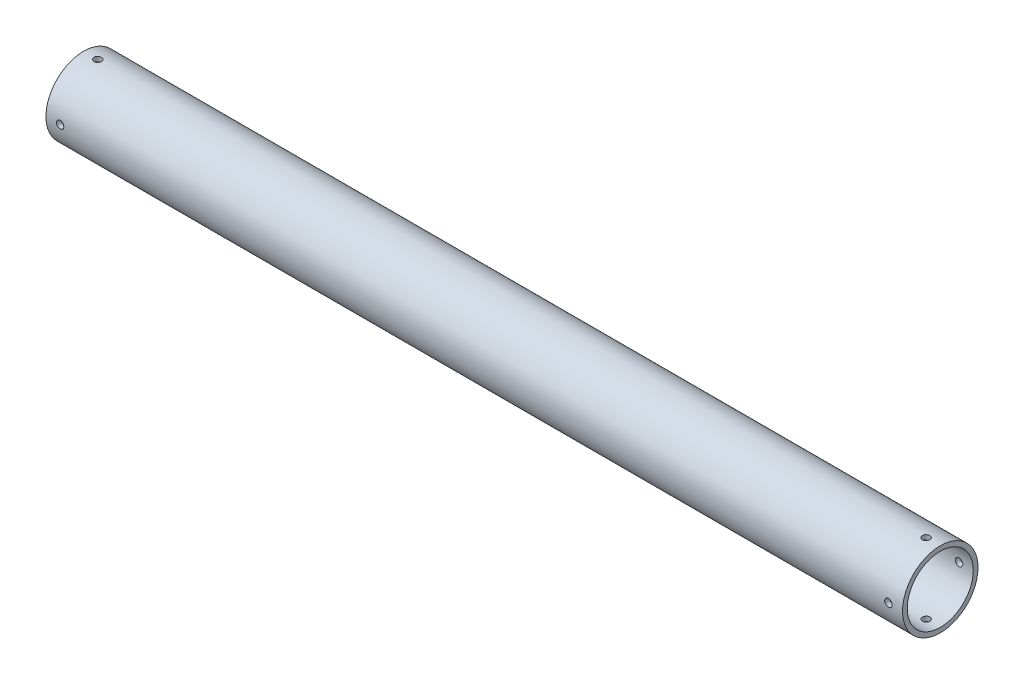
SolidWorks part; units mm, degrees
material "PC High Viscosity"
ref_plane "Front Plane" through (0, 0, 0) normal (0, 0, 1) x (1, 0, 0)
ref_plane "Top Plane" through (0, 0, 0) normal (0, 1, 0) x (1, 0, 0)
ref_plane "Right Plane" through (0, 0, 0) normal (1, 0, 0) x (0, 0, -1)
sketch "Sketch1" plane through (0, 0, 0) normal (1, 0, 0) x (0, 0, -1)
  circle A0 centre (0, 0) radius 25.4
  circle A1 centre (0, 0) radius 22.225
  dimension "D1" = 50.8
  dimension "D2" = 3.175
extrude "Boss-Extrude1" add sketch "Sketch1" along normal mid plane 576.58
sketch "Sketch2" plane through (0, 0, 0) normal (0, 0, 1) x (1, 0, 0)
  line L0 (-288.29, 25.4) -> (-288.29, -25.4) construction
  line L1 (288.29, -25.4) -> (288.29, 25.4) construction
  circle A0 centre (-278.765, 0) radius 2.4892
  circle A1 centre (278.765, 0) radius 2.4892
  point P4 (0, 0)
  dimension "D1" = 4.9784
  dimension "D2" = 9.525
  dimension "D3" = 9.525
extrude "Cut-Extrude1" cut sketch "Sketch2" against normal through all both and the other way through all
sketch "Sketch3" plane through (0, 0, 0) normal (0, 1, 0) x (1, 0, 0)
  line L3 (288.29, -22.225) -> (288.29, 22.225) construction
  line L4 (-288.29, 25.4) -> (-288.29, -25.4) construction
  circle A0 centre (-278.765, 0) radius 2.4892
  circle A1 centre (278.765, 0) radius 2.4892
  point P4 (0, 0)
  point P8 (0, 0)
  point P11 (0, 0)
  point P12 (-278.765, -4.8249)
  dimension "D1" = 4.9784
  dimension "D2" = 9.525
  dimension "D3" = 9.525
extrude "Cut-Extrude2" cut sketch "Sketch3" against normal through all both and the other way through all
